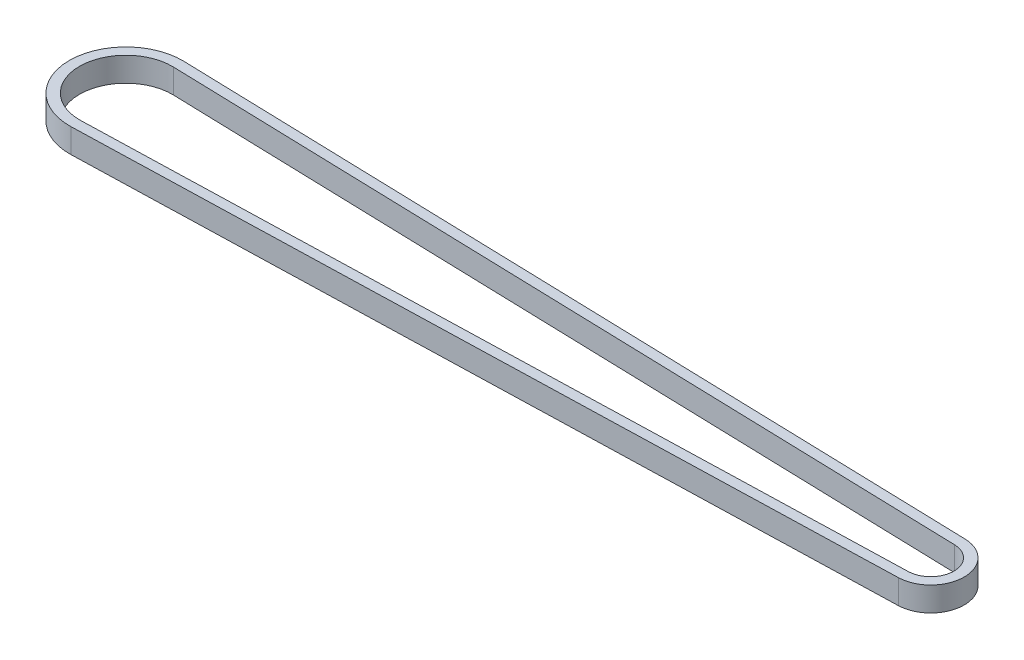
SolidWorks part; units mm, degrees
material "POLYURETHANE (11671)"
ref_plane "Front Plane" through (0, 0, 0) normal (0, 0, 1) x (1, 0, 0)
ref_plane "Top Plane" through (0, 0, 0) normal (0, 1, 0) x (1, 0, 0)
ref_plane "Right Plane" through (0, 0, 0) normal (1, 0, 0) x (0, 0, -1)
sketch "Sketch1" plane through (0, 0, 0) normal (0, 1, 0) x (1, 0, 0)
  line L0 (-99.441, 0) -> (99.441, 0) construction
  line L1 (0, 0) -> (0, 67523.6974) construction
  line L4 (-99.1112, 11.4507) -> (99.606, 5.7266)
  line L5 (-99.1112, -11.4507) -> (99.606, -5.7266)
  line L6 (0, 0) -> (0, 44.9411) construction
  line L7 (-99.0396, 13.9642) -> (99.6782, 8.2516)
  line L8 (-99.0396, -13.9642) -> (99.6782, -8.2516)
  arc A0 (-99.1112, 11.4507) -> (-99.1112, -11.4507) centre (-99.441, 0) ccw
  arc A1 (99.606, -5.7266) -> (99.606, 5.7266) centre (99.441, 0) ccw
  arc A2 (-99.0396, 13.9642) -> (-99.0396, -13.9642) centre (-99.441, 0) ccw
  arc A3 (99.6782, -8.2516) -> (99.6782, 8.2516) centre (99.441, 0) ccw
  dimension "D2" = 22.9108
  dimension "D3" = 11.4579
  dimension "D4" = 27.94
  dimension "D5" = 16.51
  dimension "D1" = 198.882
extrude "Boss-Extrude1" add sketch "Sketch1" along normal blind 5.9944
